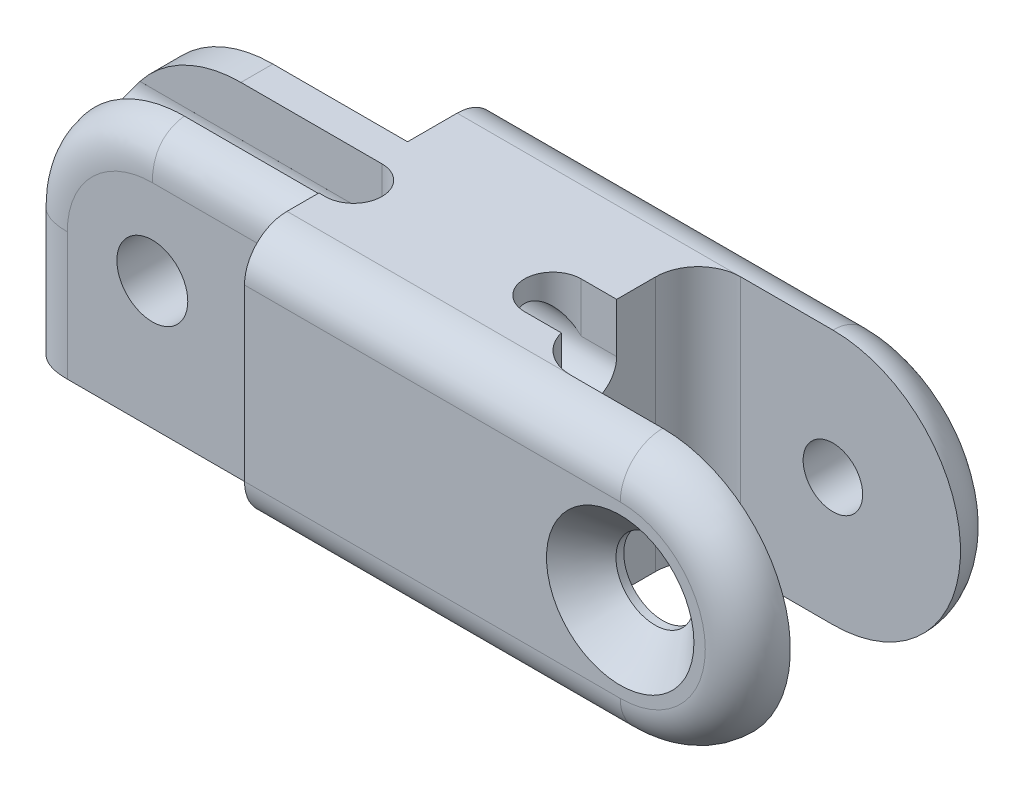
SolidWorks part; units mm, degrees
ref_plane "Front Plane" through (0, 0, 0) normal (0, 0, 1) x (1, 0, 0)
ref_plane "Top Plane" through (0, 0, 0) normal (0, 1, 0) x (1, 0, 0)
ref_plane "Right Plane" through (0, 0, 0) normal (1, 0, 0) x (0, 0, -1)
sketch "Sketch2" plane through (0, 0, 0) normal (0, 1, 0) x (1, 0, 0)
  line L0 (-8.5, 9) -> (27, 9)
  line L1 (27, 9) -> (27, 6)
  line L2 (27, 6) -> (11.5, 6)
  line L3 (8.5, 3) -> (8.5, -3)
  line L4 (11.5, -6) -> (27, -6)
  line L5 (27, -6) -> (27, -9)
  line L7 (-27, -6) -> (-27, 2.5)
  line L8 (-49.3622, 0) -> (56.3776, 0) construction
  line L9 (0, 21.2372) -> (0, -19.0689) construction
  line L10 (8.5, 3) -> (11.5, 3) construction
  line L11 (11.5, 3) -> (11.5, 6) construction
  line L16 (-8.5, -9) -> (27, -9)
  line L18 (-27, -6) -> (-8.5, -6)
  line L19 (-8.5, -6) -> (-8.5, -9)
  line L20 (-27, 2.5) -> (-8.5, 2.5)
  line L21 (-8.5, 2.5) -> (-8.5, 9)
  arc A0 (11.5, 6) -> (8.5, 3) centre (11.5, 3) ccw
  arc A1 (11.5, -6) -> (8.5, -3) centre (11.5, -3) cw
  point P13 (11.5, 3)
  dimension "D1" = 54
  dimension "D2" = 18
  dimension "D3" = 3
  dimension "D4" = 18.5
  dimension "D5" = 12
  dimension "D6" = 3
  dimension "D7" = 3
  dimension "D8" = 6.5
  dimension "D9" = 3
  dimension "D10" = 8.5
  dimension "D11" = 18.5
extrude "Boss-Extrude1" add sketch "Sketch2" along normal blind 18
sketch "Sketch5" plane through (0, 0, 9) normal (0, 0, 1) x (1, 0, 0)
  line L0 (-27, 9) -> (31.8491, 9) construction
  line L1 (-18, 18) -> (-18, 0) construction
  line L2 (27, 18) -> (27, 0) construction
  line L3 (-8.5, 18) -> (27, 18) construction
  line L4 (18, 18) -> (18, 0) construction
  line L5 (-27, 18) -> (-27, 0) construction
  line L6 (-27, 9) -> (-27, 0)
  line L7 (-27, 18) -> (-8.5, 18) construction
  line L8 (-27, 0) -> (18, 0)
  line L9 (-18, 18) -> (18, 18)
  arc A0 (-18, 18) -> (-27, 9) centre (-18, 9) ccw
  arc A1 (18, 0) -> (18, 18) centre (18, 9) ccw
  circle A2 centre (-18, 9) radius 2.5
  dimension "D2" = 5
  dimension "D1" = 9
extrude "Cut-Extrude1" cut sketch "Sketch5" against normal blind 20 flip side to cut
sketch "Sketch6" plane through (0, 0, 9) normal (0, 0, 1) x (1, 0, 0)
  line L0 (18, 0) -> (18, 18) construction
  point P4 (18, 9)
hole_wizard "CSK for M5 Countersunk Flat Head Screw1" positions "Sketch7" profile "Sketch8" countersink size "M5" standard "DIN" end condition up to next
sketch "Sketch7" plane through (0, 0, 9) normal (0, 0, 1) x (1, 0, 0)
  point P0 (18, 9)
sketch "Sketch8" plane through (18, 9, 9) normal (1, 0, 0) x (0, -1, 0)
  line L0 (0, 0) -> (0, 3)
  line L1 (0, 3) -> (2.75, 3)
  line L2 (2.75, 3) -> (2.75, 2.45)
  line L3 (2.75, 2.45) -> (5.2, 0)
  line L5 (5.2, 0) -> (0, 0)
  line L6 (-2.75, 2.45) -> (-5.2, 0) construction
  line L11 (0, -6.35) -> (0, 107.95) construction
  dimension "Thru Hole Dia." = 5.5
  dimension "Thru Hole Depth" = 3
  dimension "Near C'Sink Dia." = 10.4
  dimension "Near C'Sink Angle" = 90
hole_wizard "M5 Tapped Hole1" positions "Sketch9" profile "Sketch11" tap size "M5" standard "DIN" end condition through all
sketch "Sketch9" plane through (0, 0, 9) normal (0, 0, 1) x (1, 0, 0)
  point P0 (18, 9)
sketch "Sketch11" plane through (18, 9, 9) normal (1, 0, 0) x (0, -1, 0)
  line L0 (0, 0) -> (0, 18)
  line L1 (0, 18) -> (2.1, 18)
  line L2 (2.1, 18) -> (2.1, 3.1)
  line L3 (2.1, 3.1) -> (5.2, 0)
  line L5 (5.2, 0) -> (0, 0)
  line L6 (-2.1, 3.1) -> (-5.2, 0) construction
  line L11 (0, -6.35) -> (0, 107.95) construction
  dimension "Thru Tap Drill Dia." = 4.2
  dimension "Thru Tap Drill Depth" = 18
  dimension "Near C'Sink Dia." = 10.4
  dimension "Near C'Sink Angle" = 90
cosmetic thread "Hole Thread1" parameters "D2"=5
fillet "Fillet3" radius 3 3 edges at (-27, 4.5, 6) (-13.25, 18, 6) (-24.364, 15.364, 6) conic rho 0.5
sketch "Sketch13" plane through (8.5, 0, 0) normal (1, 0, 0) x (0, 0, -1)
  line L0 (-1.75, 21.4915) -> (-1.75, -4.5302) construction
  line L1 (-3, 18) -> (3, 18) construction
  circle A0 centre (-1.75, 14.5) radius 2
  dimension "D2" = 4
  dimension "D3" = 3.5
  dimension "D1" = 1.75
extrude "Cut-Extrude2" cut sketch "Sketch13" against normal through all both and the other way through all
sketch "Sketch14" plane through (0, 18, 0) normal (0, 1, 0) x (1, 0, 0)
  line L0 (-25.1236, 0.2504) -> (-8.0557, 0.2504)
  line L1 (-25.0557, -3.75) -> (-8.0557, -3.75)
  line L3 (-25.0557, -3.75) -> (-25.1236, 0.2504)
  arc A0 (-8.0557, -3.75) -> (-8.0557, 0.2504) centre (-8.0557, -1.7498) ccw
  spline S1 degree 3 poles (-23.5797, -3) (-23.4473, -2.8693) (-23.3242, -2.7233) (-23.1669, -2.4679) (-23.12, -2.3776) (-23.0431, -2.1872) (-23.0127, -2.0851) (-22.9764, -1.8774) (-22.9703, -1.7698) (-22.9841, -1.5572) (-23.0036, -1.4537) (-23.0944, -1.1509) (-23.1934, -0.9724) (-23.4222, -0.6565) (-23.5506, -0.5207) (-23.8219, -0.2789) (-23.9619, -0.1762) (-24.3834, 0.0849) (-24.6717, 0.1991) (-25.0706, 0.2557) (-25.2006, 0.2556) (-25.4459, 0.209) (-25.5594, 0.1634) (-25.769, 0.0188) (-25.8624, -0.0793) (-26.0226, -0.3256) (-26.0911, -0.4779) (-26.1703, -0.7331) (-26.1932, -0.8231) (-26.2322, -1.0133) (-26.2481, -1.1133) (-26.2724, -1.3157) (-26.281, -1.419) (-26.2912, -1.6301) (-26.2926, -1.7379) (-26.2863, -2.055) (-26.2677, -2.2665) (-26.2021, -2.6575) (-26.1546, -2.8399) (-26.0922, -3) knots 0 0 0 0 0.0625 0.0625 0.09375 0.09375 0.125 0.125 0.15625 0.15625 0.1875 0.1875 0.25 0.25 0.3125 0.3125 0.375 0.375 0.5 0.5 0.5625 0.5625 0.625 0.625 0.6875 0.6875 0.75 0.75 0.78125 0.78125 0.8125 0.8125 0.84375 0.84375 0.875 0.875 0.9375 0.9375 1 1 1 1 construction
  spline S2 degree 3 poles (-26.0922, -3) (-26.0381, -3.1387) (-25.9701, -3.2552) (-25.8108, -3.4526) (-25.7195, -3.5323) (-25.5254, -3.6532) (-25.4205, -3.6957) (-25.205, -3.7461) (-25.094, -3.7546) (-24.7507, -3.7337) (-24.5173, -3.6588) (-24.0422, -3.4019) (-23.8092, -3.2263) (-23.5797, -3) knots 0 0 0 0 0.125 0.125 0.25 0.25 0.375 0.375 0.5 0.5 0.75 0.75 1 1 1 1 construction
  dimension "D2" = 2.0002
  dimension "D1" = 17
extrude "Cut-Extrude3" cut sketch "Sketch14" against normal blind 3.5
sketch "Sketch15" plane through (0, 18, 0) normal (0, 1, 0) x (1, 0, 0)
sketch "Sketch16" plane through (0, 18, 0) normal (0, 1, 0) x (1, 0, 0)
  line L0 (-8.0769, -1.75) -> (29.6251, -1.75) construction
  line L1 (6, 0.25) -> (19.0559, 0.25)
  line L3 (6, -3.75) -> (19.0559, -3.75)
  line L4 (19.0559, 0.25) -> (19.0559, -3.75)
  line L5 (8.5, -3) -> (8.5, 3) construction
  arc A0 (6, 0.25) -> (6, -3.75) centre (6, -1.75) ccw
  dimension "D2" = 4
  dimension "D1" = 1.75
  dimension "D3" = 2.5
extrude "Cut-Extrude4" cut sketch "Sketch16" against normal blind 3.5
fillet "Fillet4" radius 3 6 edges at (4.75, 0, 9) (27, 9, 9) (4.75, 18, 9) (4.75, 0, -9) (27, 9, -9) (4.75, 18, -9)
